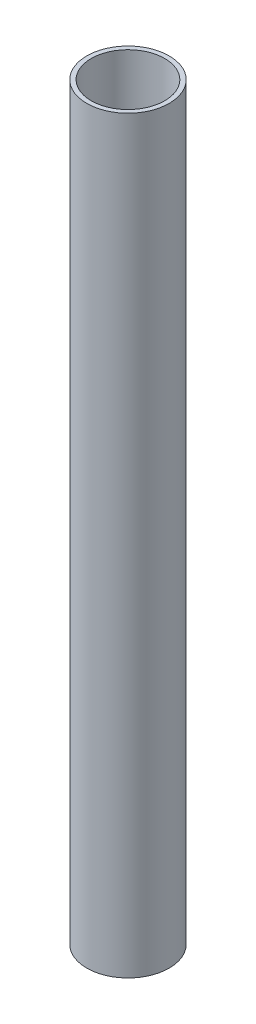
SolidWorks part; units mm, degrees
material "ПВХ 0.007 Смягченный"
ref_plane "Спереди" through (0, 0, 0) normal (0, 0, 1) x (1, 0, 0)
ref_plane "Сверху" through (0, 0, 0) normal (0, 1, 0) x (1, 0, 0)
ref_plane "Справа" through (0, 0, 0) normal (1, 0, 0) x (0, 0, -1)
sketch "Эскиз1" plane through (0, 0, 0) normal (0, 1, 0) x (1, 0, 0)
  circle A0 centre (0, 0) radius 55
  circle A1 centre (0, 0) radius 49
  dimension "ExDBody" = 110
  dimension "InDBody" = 98
extrude "Бобышка-Вытянуть1" add sketch "Эскиз1" along normal blind 1000
